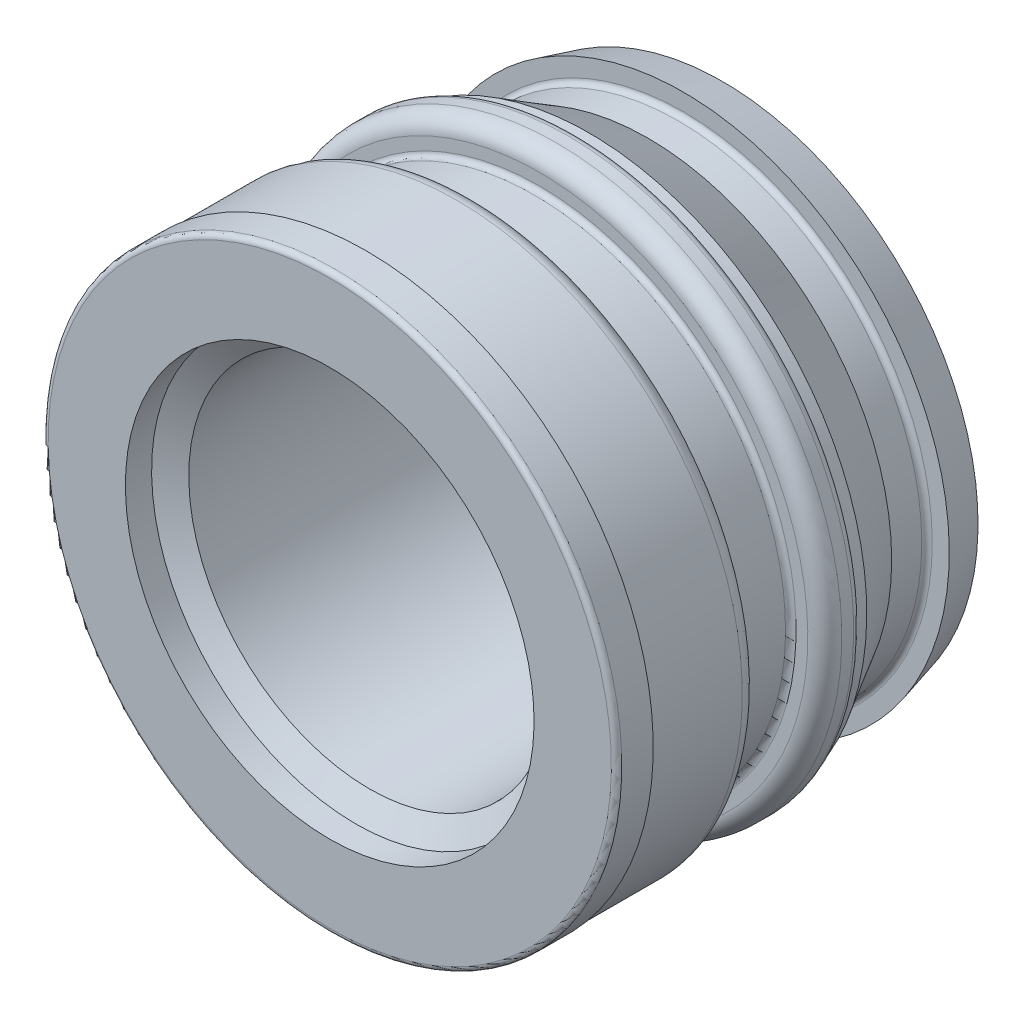
SolidWorks part; units mm, degrees
ref_plane "Front Plane" through (0, 0, 0) normal (0, 0, 1) x (1, 0, 0)
ref_plane "Top Plane" through (0, 0, 0) normal (0, 1, 0) x (1, 0, 0)
ref_plane "Right Plane" through (0, 0, 0) normal (1, 0, 0) x (0, 0, -1)
sketch "Sketch1" plane through (0, 0, 0) normal (1, 0, 0) x (0, 0, -1)
  line L0 (1.905, 0) -> (-1.905, 0) construction
  line L1 (-1.905, 2.7813) -> (-1.905, -2.7813) construction
  line L3 (1.905, 2.476) -> (1.905, -2.476) construction
  line L4 (-1.905, 2.7813) -> (-1.5494, 2.7813) construction
  line L5 (-1.5494, 2.7813) -> (-1.5494, 2.7686) construction
  line L6 (-1.5494, 2.7686) -> (-0.508, 2.7686) construction
  line L7 (-0.508, 2.7686) -> (-0.508, 2.4384) construction
  line L8 (-0.508, 2.4384) -> (0.127, 2.4384) construction
  line L9 (0.127, 2.4384) -> (0.127, 2.7686) construction
  line L10 (0.127, 2.7686) -> (0.4826, 2.7686) construction
  line L12 (-1.651, -1.9812) -> (-1.519, -1.7526) construction
  line L13 (-1.519, -1.7526) -> (1.6764, -1.7526) construction
  line L14 (1.6764, -1.7526) -> (1.905, -1.9812) construction
  line L15 (-1.519, -1.7526) -> (-1.519, -0.9589) construction
  line L16 (-1.651, -1.9812) -> (-1.905, -1.9812) construction
  line L21 (1.1815, 2.3622) -> (1.524, 2.3622) construction
  line L22 (1.524, 2.3622) -> (1.524, 2.5781) construction
  line L23 (1.524, 2.5781) -> (1.905, 2.476) construction
  line L24 (0.4826, 2.7686) -> (0.4826, 2.6924) construction
  line L25 (0.4826, 2.6924) -> (0.6096, 2.6924) construction
  line L26 (0.6096, 2.6924) -> (1.1815, 2.3622) construction
  point P4 (0, 0)
  dimension "Diameter (A)" = 5.5626
  dimension "Installed Length" = 3.81
  dimension "Head Length" = 0.3556
  dimension "Knurl Band OD" = 5.5372
  dimension "Knurl Band_1 Length" = 1.0414
  dimension "Relief Depth" = 0.3302
  dimension "Relief Length" = 0.635
  dimension "Thread Size" = 3.5052
  dimension "Thread Pitch" = 0.7937
  dimension "C'Sink Dia (B)" = 3.9624
  dimension "C'Sink (A)" = 60
  dimension "C'Bore" = 3.9624
  dimension "C'Bore Depth" = 0.254
  dimension "Barb Angle" = 15
  dimension "End Barb Length" = 0.381
  dimension "End Barb OD" = 5.1562
  dimension "End Barb Relief" = 4.7244
  dimension "C'Sink (B)" = 45
  dimension "Knurl Band_2 Length" = 0.3556
  dimension "Knurl Band Step" = 0.0762
  dimension "Stepdown Taper" = 30
  dimension "Step Length" = 0.127
sketch "Sketch2" plane through (0, 0, 0) normal (1, 0, 0) x (0, 0, -1)
  line L0 (0.6096, 2.6924) -> (1.1815, 2.3622) construction
  line L3 (1.524, 2.5781) -> (1.905, 2.476) construction
  line L15 (1.524, 2.3622) -> (1.524, 2.5781) construction
  line L19 (0.4826, 2.6924) -> (0.6096, 2.6924) construction
  line L27 (1.1815, 2.3622) -> (1.524, 2.3622) construction
  line L28 (0.4826, 2.7686) -> (0.4826, 2.6924) construction
  line L30 (0.6096, 2.6924) -> (1.1815, 2.3622)
  line L31 (-0.6731, 2.7686) -> (-0.6731, 2.4384) construction
  line L33 (0.2921, 2.7686) -> (0.4064, 2.7686)
  line L34 (0.4826, 2.6924) -> (0.6096, 2.6924)
  line L37 (0.127, 2.7686) -> (0.4826, 2.7686) construction
  line L38 (0.127, 2.4384) -> (0.127, 2.7686) construction
  line L39 (-0.508, 2.4384) -> (0.127, 2.4384) construction
  line L40 (-0.508, 2.7686) -> (-0.508, 2.4384) construction
  line L41 (-1.5494, 2.7686) -> (-0.508, 2.7686) construction
  line L42 (-1.5494, 2.7813) -> (-1.5494, 2.7686) construction
  line L43 (-1.905, 2.7813) -> (-1.5494, 2.7813) construction
  line L44 (1.524, 2.5781) -> (1.905, 2.476)
  line L45 (1.524, 2.413) -> (1.524, 2.5781)
  line L46 (1.1815, 2.3622) -> (1.4732, 2.3622)
  line L51 (0.2921, 2.7686) -> (0.4826, 2.7686) construction
  line L52 (0.127, 2.4892) -> (0.127, 2.6035)
  line L53 (-0.4572, 2.4384) -> (0.0762, 2.4384)
  line L54 (-0.508, 2.6035) -> (-0.508, 2.4892)
  line L55 (-1.5494, 2.7686) -> (-0.6731, 2.7686)
  line L56 (-1.5494, 2.7813) -> (-1.5494, 2.7686)
  line L57 (-1.8542, 2.7813) -> (-1.5494, 2.7813)
  line L58 (-1.905, 0) -> (1.905, 0) construction
  line L59 (-1.905, 2.7305) -> (-1.905, 1.9812)
  line L60 (-1.905, 2.7813) -> (-1.905, -2.7813) construction
  line L61 (-1.905, 1.9812) -> (-1.651, 1.9812)
  line L62 (-1.651, 1.9812) -> (-1.519, 1.7526)
  line L63 (-1.519, 1.7526) -> (1.6764, 1.7526)
  line L64 (1.6764, 1.7526) -> (1.905, 1.9812)
  line L65 (1.905, 2.476) -> (1.905, -2.476) construction
  line L66 (1.905, 1.9812) -> (1.905, 2.476)
  line L67 (-1.651, -1.9812) -> (-1.905, -1.9812) construction
  line L68 (-1.651, -1.9812) -> (-1.519, -1.7526) construction
  line L69 (1.6764, -1.7526) -> (1.905, -1.9812) construction
  line L70 (0, -1.7526) -> (0, 1.7526) construction
  line L71 (-1.519, -1.7526) -> (1.6764, -1.7526) construction
  line L72 (0.4826, 2.7686) -> (0.4826, 2.6924) construction
  arc A1 (0.2921, 2.7686) -> (0.127, 2.6035) centre (0.2921, 2.6035) ccw
  arc A2 (-0.508, 2.6035) -> (-0.6731, 2.7686) centre (-0.6731, 2.6035) ccw
  arc A3 (-1.8542, 2.7813) -> (-1.905, 2.7305) centre (-1.8542, 2.7305) ccw
  arc A4 (1.4732, 2.3622) -> (1.524, 2.413) centre (1.4732, 2.413) ccw
  arc A5 (0.4826, 2.6924) -> (0.4064, 2.7686) centre (0.4064, 2.6924) ccw
  arc A6 (0.127, 2.4892) -> (0.0762, 2.4384) centre (0.0762, 2.4892) cw
  arc A7 (-0.4572, 2.4384) -> (-0.508, 2.4892) centre (-0.4572, 2.4892) cw
  point P64 (0, 0)
  dimension "D1" = 0.0508
  dimension "D2" = 0.0508
  dimension "D3" = 0.0508
  dimension "Knurl Length" = 2.032
revolve "Revolve1" add sketch "Sketch2" angle 360 about L58
sketch "Sketch3" plane through (0, 0, 0) normal (0, 0, 1) x (1, 0, 0)
  line L0 (0, -1.7526) -> (0, 0) construction
  line L1 (0, 0) -> (0.8763, -1.5178) construction
  line L2 (0, 2.476) -> (0, -2.476) construction
  circle A0 centre (0, 0) radius 1.7526 construction
  point P0 (0.8763, -1.5178)
  dimension "D1" = 30
sketch "Sketch4" [suppressed] plane through (0, 0, 1.905) normal (0, 0, 1) x (1, 0, 0)
  circle A0 centre (0, 0) radius 1.7526 construction
  circle A1 centre (0, 0) radius 1.7526
curve "Helix/Spiral1" [suppressed] pitch 0.7937 height 4.6037 turns 5.8
sketch "Sketch5" [suppressed] plane through (0, 0, 0) normal (1, 0, 0) x (0, 0, -1)
  line L0 (-2.6739, 1.7956) -> (-2.2771, 1.1082) construction
  line L1 (-2.2771, 1.1082) -> (-1.8802, 1.7956) construction
  line L2 (-1.8802, 1.7956) -> (-2.6739, 1.7956) construction
  line L3 (-2.6243, 1.7096) -> (-1.9298, 1.7096) construction
  line L4 (-2.2771, 1.7956) -> (-2.2771, 1.7096) construction
  line L5 (-2.2771, 1.7096) -> (-2.2771, 1.1941) construction
  line L6 (-2.2771, 1.1941) -> (-2.2771, 1.1082) construction
  line L7 (-2.3267, 1.1941) -> (-2.2275, 1.1941)
  line L8 (-2.6491, 1.7526) -> (-1.905, 1.7526)
  line L9 (-2.2275, 1.1941) -> (-1.905, 1.7526)
  line L10 (-2.3267, 1.1941) -> (-2.6491, 1.7526)
  line L15 (1.6764, 1.7526) -> (-1.519, 1.7526) construction
  line L16 (-1.905, 2.7813) -> (-1.905, -2.7813) construction
  point P12 (-2.2771, 1.7526)
  dimension "D1" = 0.7937
  dimension "D2" = 0.0992
sweep "Sweep1" [suppressed] add profiles "Sketch5" path "Helix/Spiral1"
ref_plane "Plane1" [suppressed] through (0, 0, 1.651) normal (0, 0, 1) x (1, 0, 0)
sketch "Sketch6" [suppressed] plane through (0, 0, 1.651) normal (0, 0, 1) x (1, 0, 0)
  circle A0 centre (0, 0) radius 1.9812
extrude "Cut-Extrude1" [suppressed] cut sketch "Sketch6" against normal through all draft 60 and the other way through all
sketch "Sketch7" [suppressed] plane through (0, 0, -1.905) normal (0, 0, -1) x (-1, 0, 0)
  circle A1 centre (0, 0) radius 1.9812
  circle A2 centre (0, 0) radius 1.9812 construction
extrude "Cut-Extrude2" [suppressed] cut sketch "Sketch7" against normal through all draft 45 and the other way through all
ref_plane "Plane2" [suppressed] through (0, 0, 1.5494) normal (0, 0, 1) x (1, 0, 0)
sketch "Sketch8" [suppressed] plane through (0, 0, 1.5494) normal (0, 0, 1) x (1, 0, 0)
  circle A1 centre (0, 0) radius 2.7686
  circle A2 centre (0, 0) radius 2.7686 construction
curve "Helix/Spiral2" [suppressed] pitch 16.256 height 2.032 turns 0.125
sketch "Sketch9" [suppressed] plane through (0, 0, 1.5494) normal (0, 0, 1) x (1, 0, 0)
  line L0 (-0.2315, 2.7716) -> (-0.0459, 2.6316)
  line L1 (0.0459, 2.6316) -> (0.2315, 2.7716)
  line L3 (0, 0) -> (0, 2.6924) construction
  circle A0 centre (0, 0) radius 2.6924 construction
  circle A1 centre (0, 0) radius 2.6924 construction
  arc A2 (-0.2315, 2.7716) -> (0.2315, 2.7716) centre (0, 0) cw
  arc A3 (-0.0459, 2.6316) -> (0.0459, 2.6316) centre (0, 2.6924) ccw
  circle A5 centre (0, 0) radius 2.7813 construction
  dimension "D1" = 0.0762
  dimension "D2" = 0.4635
sweep "Cut-Sweep1" [suppressed] cut profiles "Sketch9" path "Helix/Spiral2"
pattern_circular "CirPattern1" [suppressed] count 32 over 360 of bodies 140
equation "\"D3@Helix/Spiral1\"=\"Installed Length@Sketch1\" + \"Thread Pitch@Sketch1\""
equation "\"D4@Helix/Spiral1\"=\"Thread Pitch@Sketch1\""
equation "\"D2@Sketch5\" = \"D1@Sketch5\" / 8"
equation "\"D1@Sketch5\" = \"Thread Pitch@Sketch1\""
equation "\"D3@Cut-Extrude1\"=\"C'Sink (A)@Sketch1\""
equation "\"D3@Cut-Extrude2\"=\"C'Sink (B)@Sketch1\""
equation "\"D2@Sketch9\"=\"Diameter (A)@Sketch1\" / 12"
equation "\"D1@CirPattern1\"= ( ( \"Diameter (A)@Sketch1\" * pi ) + 0.004 ) / ( ( 0.08 * \"Diameter (A)@Sketch1\" ) + 0.004 )"
equation "\"D3@Helix/Spiral2\"=\"Knurl Length@Sketch2\""
